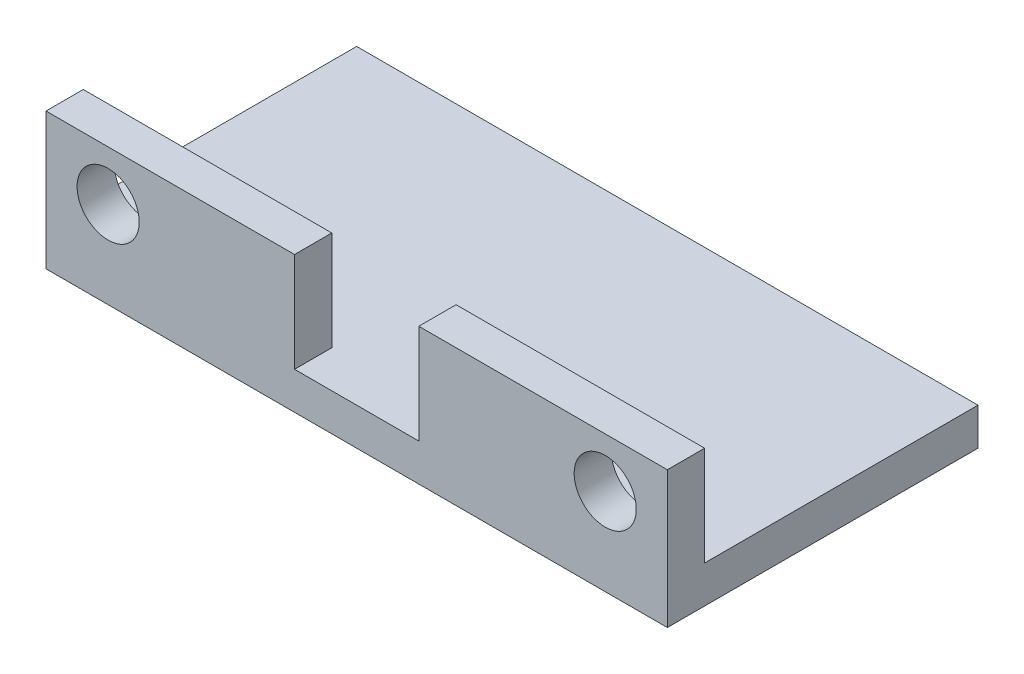
SolidWorks part; units mm, degrees
ref_plane "Front Plane" through (0, 0, 0) normal (0, 0, 1) x (1, 0, 0)
ref_plane "Top Plane" through (0, 0, 0) normal (0, 1, 0) x (1, 0, 0)
ref_plane "Right Plane" through (0, 0, 0) normal (1, 0, 0) x (0, 0, -1)
sketch "Sketch1" plane through (0, 0, 0) normal (0, 1, 0) x (1, 0, 0)
  line L1 (-31.75, 15.875) -> (31.75, 15.875)
  line L2 (-31.75, 15.875) -> (-31.75, -15.875)
  line L3 (-31.75, -15.875) -> (31.75, -15.875)
  line L4 (31.75, 15.875) -> (31.75, -15.875)
  line L5 (-31.75, 15.875) -> (31.75, -15.875) construction
  line L6 (-31.75, -15.875) -> (31.75, 15.875) construction
  point P0 (0, 0)
  dimension "D1" = 63.5
  dimension "D2" = 31.75
extrude "Boss-Extrude1" add sketch "Sketch1" along normal blind 3.81
sketch "Sketch2" plane through (0, 3.81, 0) normal (0, 1, 0) x (1, 0, 0)
  line L5 (-31.75, -15.875) -> (31.75, -15.875) construction
  line L6 (-6.35, -15.875) -> (-31.75, -15.875)
  line L7 (-6.35, -15.875) -> (-6.35, -12.065)
  line L8 (-6.35, -12.065) -> (-31.75, -12.065)
  line L9 (-31.75, -15.875) -> (-31.75, -12.065)
  line L10 (-31.75, 15.875) -> (-31.75, -15.875) construction
  line L11 (6.35, -15.875) -> (31.75, -15.875)
  line L12 (6.35, -15.875) -> (6.35, -12.065)
  line L13 (6.35, -12.065) -> (31.75, -12.065)
  line L14 (31.75, -15.875) -> (31.75, -12.065)
  line L15 (31.75, -15.875) -> (31.75, 15.875) construction
  dimension "D1" = 3.81
  dimension "D2" = 25.4
  dimension "D3" = 25.4
  dimension "D4" = 25.4
extrude "Boss-Extrude2" add sketch "Sketch2" along normal blind 10.16
sketch "Sketch3" plane through (0, 0, 12.065) normal (0, 0, -1) x (-1, 0, 0)
  line L0 (-25.4, 8.89) -> (25.4, 8.89) construction
  line L6 (-31.75, 13.97) -> (-6.35, 13.97) construction
  circle A0 centre (25.4, 8.89) radius 3.175
  circle A1 centre (-25.4, 8.89) radius 3.175
  point P4 (0, 8.89)
  dimension "D1" = 6.35
  dimension "D2" = 50.8
  dimension "D4" = 5.08
extrude "Cut-Extrude1" cut sketch "Sketch3" against normal up to surface (3.81 mm away) up to face at (0, 7.9375, 15.875)
